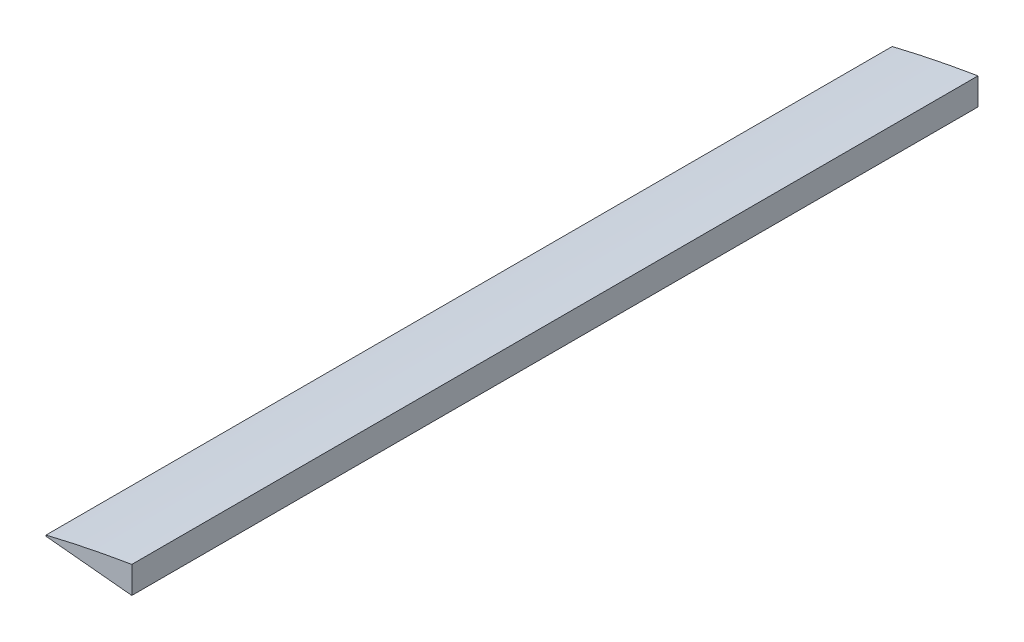
SolidWorks part; units mm, degrees
ref_plane "Front Plane" through (0, 0, 0) normal (0, 0, 1) x (1, 0, 0)
ref_plane "Top Plane" through (0, 0, 0) normal (0, 1, 0) x (1, 0, 0)
ref_plane "Right Plane" through (0, 0, 0) normal (1, 0, 0) x (0, 0, -1)
sketch "Sketch1" plane through (0, 0, 0) normal (0, 0, 1) x (1, 0, 0)
  line L0 (-176.6195, 13.0231) -> (-176.6195, -6.4544)
  line L1 (-238.675, 0.3812) -> (-238.675, -0.3751)
  spline S0 degree 3 poles (-176.6195, 13.0231) (-178.4319, 12.7225) (-182.8419, 11.9911) (-189.6921, 10.7708) (-197.0149, 9.4107) (-203.8537, 8.0796) (-210.1682, 6.8004) (-215.9209, 5.5913) (-221.0778, 4.4715) (-225.609, 3.4587) (-229.488, 2.5698) (-232.6924, 1.8199) (-235.2039, 1.2222) (-237.0081, 0.7872) (-238.0864, 0.525) (-238.5621, 0.4088) (-238.675, 0.3812) knots 0 0 0 0 0.087007 0.211705 0.329527 0.439741 0.541661 0.634652 0.718135 0.791585 0.85454 0.906603 0.947445 0.976805 0.994497 1 1 1 1
  spline S1 degree 3 poles (-176.6195, -6.4544) (-178.1888, -6.3121) (-182.3599, -5.934) (-188.9904, -5.3179) (-196.3547, -4.6242) (-203.2487, -3.9636) (-209.6287, -3.3428) (-215.4538, -2.7672) (-220.6864, -2.2426) (-225.2928, -1.7737) (-229.243, -1.3675) (-232.5108, -1.0239) (-235.0757, -0.761) (-236.9188, -0.5487) (-238.0316, -0.4591) (-238.5336, -0.3746) (-238.6667, -0.3751) (-238.675, -0.3751) knots 0 0 0 0 0.075811 0.201508 0.320388 0.431695 0.534719 0.628797 0.713321 0.78774 0.851567 0.90438 0.945827 0.975633 0.993597 0.999599 1 1 1 1
extrude "Boss-Extrude1" add sketch "Sketch1" along normal blind 612
